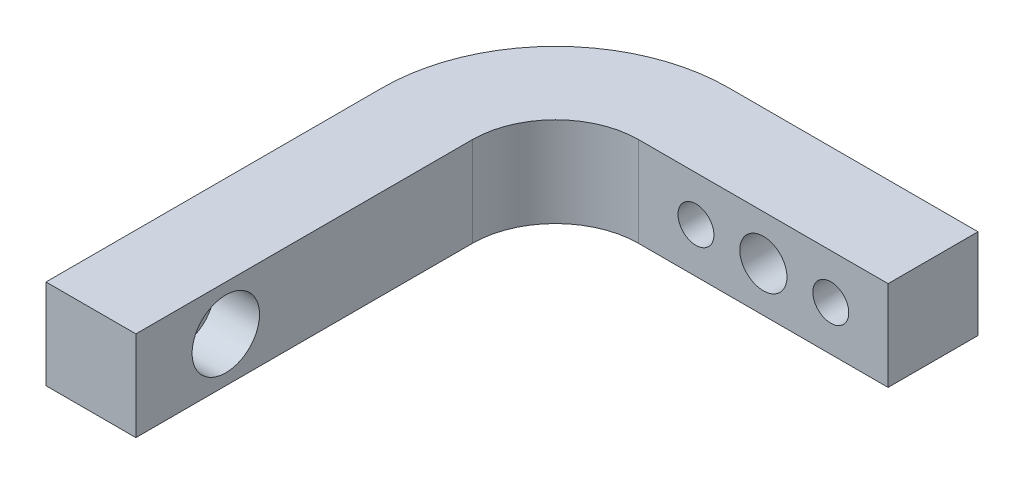
SolidWorks part; units mm, degrees
ref_plane "Front Plane" through (0, 0, 0) normal (0, 0, 1) x (1, 0, 0)
ref_plane "Top Plane" through (0, 0, 0) normal (0, 1, 0) x (1, 0, 0)
ref_plane "Right Plane" through (0, 0, 0) normal (1, 0, 0) x (0, 0, -1)
ref_axis "Z" through (0, 0, -2.267) along (0, 0, 1)
sketch "Sketch1" plane through (0, 0, 0) normal (0, 1, 0) x (1, 0, 0)
  line L0 (-11.1, 0) -> (11.1, 0)
  line L1 (-26.5, -15.4) -> (-26.5, -45.34)
  line L2 (-26.5, -45.34) -> (-18.5, -45.34)
  line L3 (-18.5, -45.34) -> (-18.5, -15.4)
  line L4 (-11.1, -8) -> (11.1, -8)
  line L5 (0, -8) -> (0, 0) construction
  line L6 (18.5, -45.34) -> (18.5, -15.4) construction
  line L7 (26.5, -45.34) -> (18.5, -45.34) construction
  line L8 (26.5, -15.4) -> (26.5, -45.34) construction
  line L9 (11.1, 0) -> (11.1, -8)
  arc A0 (-11.1, 0) -> (-26.5, -15.4) centre (-11.1, -15.4) ccw
  arc A1 (-18.5, -15.4) -> (-11.1, -8) centre (-11.1, -15.4) cw
  arc A2 (18.5, -15.4) -> (11.1, -8) centre (11.1, -15.4) ccw construction
  arc A3 (11.1, 0) -> (26.5, -15.4) centre (11.1, -15.4) cw construction
  dimension "D3" = 7.4
  dimension "D1" = 37
  dimension "D2" = 8
  dimension "D4" = 37.34
extrude "Boss-Extrude1" add sketch "Sketch1" along normal blind 4 and the other way blind 4
sketch "Sketch2" plane through (-18.5, 0, 0) normal (-1, 0, 0) x (0, 0, 1)
  line L1 (20.68, 0) -> (-20.68, 0) construction
  line L2 (0, -4.4) -> (0, 4.4) construction
  circle A0 centre (37.34, 0) radius 1.75
  dimension "D1" = 3.5
  dimension "D2" = 37.34
extrude "Cut-Extrude1" cut sketch "Sketch2" against normal through all both and the other way through all
ref_axis "Axis2" through (-60.1767, 0, 37.34) along (1, 0, 0)
sketch "Sketch3" plane through (0, 0, 0) normal (0, 0, -1) x (-1, 0, 0)
  line L0 (-6, 0) -> (6, 0) construction
  circle A0 centre (0, 0) radius 2.1
  circle A1 centre (-6, 0) radius 1.6
  circle A2 centre (6, 0) radius 1.6
  dimension "D1" = 4.2
  dimension "D3" = 3.2
  dimension "D2" = 12
extrude "Cut-Extrude2" cut sketch "Sketch3" against normal through all
sketch "Sketch4" plane through (-18.5, 0, 0) normal (1, 0, 0) x (0, 0, -1)
  circle A0 centre (-37.34, 0) radius 3
  circle A1 centre (-37.34, 0) radius 1.75 construction
  dimension "D1" = 6
extrude "Cut-Extrude3" cut sketch "Sketch4" against normal blind 4
equation "\"width\"= \"EyeDiameter\" + \"EyeClearance\""
equation "\"prongwidth\"= 8"
equation "\"D2@Sketch1\"=\"prongwidth\""
equation "\"D3@Sketch1\"=\"width\"/5"
equation "\"pronglength\"= \"BasePlaneDistance\"'model implicitly adds clearance (of prongwidth) to the hole drilled at the baseplanedistance"
equation "\"D4@Sketch1\"=\"pronglength\""
equation "\"D1@Boss-Extrude1\"=\"prongwidth\"/2"
equation "\"D2@Boss-Extrude1\"=\"prongwidth\"/2"
equation "\"lbracket-plane-to-axis\"= \"BasePlaneDistance\""
equation "\"D2@Sketch2\"=\"lbracket-plane-to-axis\""
equation "\"EyeDiameter\" = 35"
equation "\"BasePlaneDistance\" = \"EyeDiameter\"/2+19.84"
equation "\"EyeClearance\" = 2"
equation "\"D1@Sketch1\"=\"EyeDiameter\"+\"EyeClearance\""
